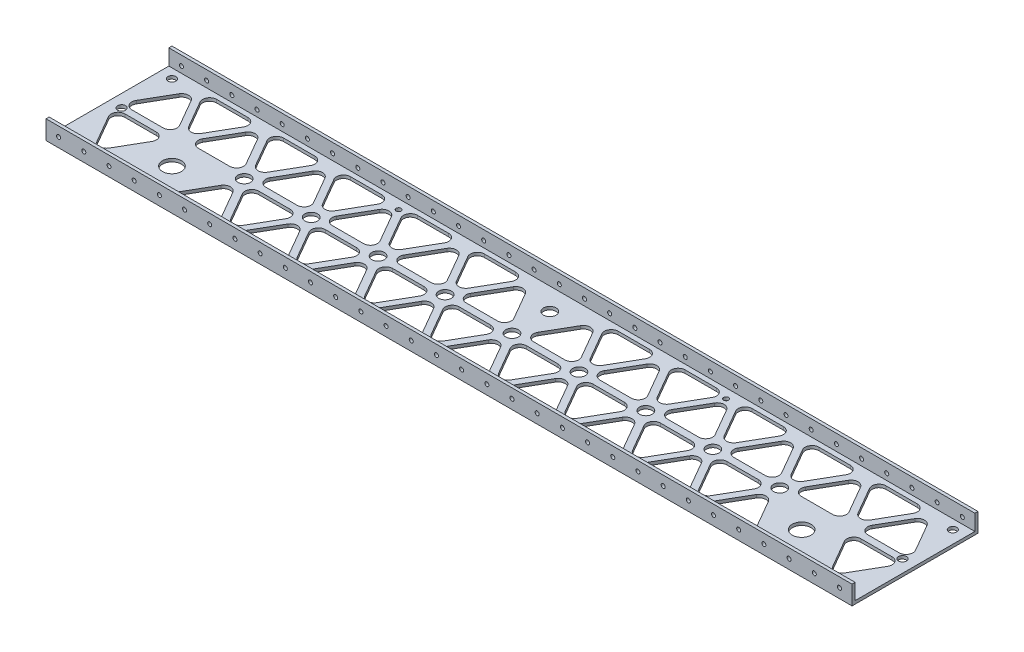
SolidWorks part; units mm, degrees
ref_plane "Front Plane" through (0, 0, 0) normal (0, 0, 1) x (1, 0, 0)
ref_plane "Top Plane" through (0, 0, 0) normal (0, 1, 0) x (1, 0, 0)
ref_plane "Right Plane" through (0, 0, 0) normal (1, 0, 0) x (0, 0, -1)
ref_plane "Plane1" through (0, -6.35, 0) normal (0, 1, 0) x (1, 0, 0)
sketch "Sketch1" plane through (0, -6.35, 0) normal (0, 1, 0) x (1, 0, 0)
  line L0 (-406.4, 63.5) -> (-406.4, -63.5)
  line L1 (-406.4, -63.5) -> (406.4, -63.5)
  line L2 (406.4, -63.5) -> (406.4, 63.5)
  line L3 (406.4, 63.5) -> (-406.4, 63.5)
extrude "Boss-Extrude1" add sketch "Sketch1" against normal blind 19.05
sketch "Sketch2" plane through (-406.4, 0, 0) normal (-1, 0, 0) x (0, 0, 1)
  line L0 (60.375, -6.35) -> (-60.375, -6.35)
  line L1 (-60.375, -6.35) -> (-60.375, -22.275)
  line L2 (-60.375, -22.275) -> (60.375, -22.275)
  line L3 (60.375, -22.275) -> (60.375, -6.35)
extrude "Cut-Extrude1" cut sketch "Sketch2" against normal through all
sketch "Sketch3" plane through (0, -22.275, 0) normal (0, 1, 0) x (-1, 0, 0)
  line L0 (-343.5622, -17.5) -> (-359.3671, -44.875)
  line L1 (-353.305, -55.375) -> (-321.695, -55.375)
  line L2 (-315.6329, -44.875) -> (-331.4378, -17.5)
  arc A0 (-359.3671, -44.875) -> (-353.305, -55.375) centre (-353.305, -48.375) ccw
  arc A1 (-321.695, -55.375) -> (-315.6329, -44.875) centre (-321.695, -48.375) ccw
  arc A2 (-331.4378, -17.5) -> (-343.5622, -17.5) centre (-337.5, -21) ccw
extrude "Cut-Extrude2" cut sketch "Sketch3" against normal through all
sketch "Sketch4" plane through (0, -22.275, 0) normal (0, 1, 0) x (-1, 0, 0)
  line L0 (-349.1414, 14) -> (-364.9463, 41.375)
  line L1 (-377.0707, 41.375) -> (-392.8756, 14)
  line L2 (-386.8135, 3.5) -> (-355.2035, 3.5)
  arc A0 (-364.9463, 41.375) -> (-377.0707, 41.375) centre (-371.0085, 37.875) ccw
  arc A1 (-392.8756, 14) -> (-386.8135, 3.5) centre (-386.8135, 10.5) ccw
  arc A2 (-355.2035, 3.5) -> (-349.1414, 14) centre (-355.2035, 10.5) ccw
extrude "Cut-Extrude3" cut sketch "Sketch4" against normal through all
sketch "Sketch5" plane through (0, -22.275, 0) normal (0, 1, 0) x (-1, 0, 0)
  line L0 (-364.9463, -41.375) -> (-349.1414, -14)
  line L1 (-355.2035, -3.5) -> (-386.8135, -3.5)
  line L2 (-392.8756, -14) -> (-377.0707, -41.375)
  arc A0 (-349.1414, -14) -> (-355.2035, -3.5) centre (-355.2035, -10.5) ccw
  arc A1 (-386.8135, -3.5) -> (-392.8756, -14) centre (-386.8135, -10.5) ccw
  arc A2 (-377.0707, -41.375) -> (-364.9463, -41.375) centre (-371.0085, -37.875) ccw
extrude "Cut-Extrude4" cut sketch "Sketch5" against normal through all
sketch "Sketch6" plane through (0, -22.275, 0) normal (0, 1, 0) x (-1, 0, 0)
  line L0 (364.9463, 41.375) -> (349.1414, 14)
  line L1 (355.2035, 3.5) -> (386.8135, 3.5)
  line L2 (392.8756, 14) -> (377.0707, 41.375)
  arc A0 (349.1414, 14) -> (355.2035, 3.5) centre (355.2035, 10.5) ccw
  arc A1 (386.8135, 3.5) -> (392.8756, 14) centre (386.8135, 10.5) ccw
  arc A2 (377.0707, 41.375) -> (364.9463, 41.375) centre (371.0085, 37.875) ccw
extrude "Cut-Extrude5" cut sketch "Sketch6" against normal through all
sketch "Sketch7" plane through (0, -22.275, 0) normal (0, 1, 0) x (-1, 0, 0)
  line L0 (349.1414, -14) -> (364.9463, -41.375)
  line L1 (377.0707, -41.375) -> (392.8756, -14)
  line L2 (386.8135, -3.5) -> (355.2035, -3.5)
  arc A0 (364.9463, -41.375) -> (377.0707, -41.375) centre (371.0085, -37.875) ccw
  arc A1 (392.8756, -14) -> (386.8135, -3.5) centre (386.8135, -10.5) ccw
  arc A2 (355.2035, -3.5) -> (349.1414, -14) centre (355.2035, -10.5) ccw
extrude "Cut-Extrude6" cut sketch "Sketch7" against normal through all
sketch "Sketch8" plane through (0, -22.275, 0) normal (0, 1, 0) x (-1, 0, 0)
  line L0 (331.4378, -17.5) -> (315.6329, -44.875)
  line L1 (321.695, -55.375) -> (353.305, -55.375)
  line L2 (359.3671, -44.875) -> (343.5622, -17.5)
  arc A0 (315.6329, -44.875) -> (321.695, -55.375) centre (321.695, -48.375) ccw
  arc A1 (353.305, -55.375) -> (359.3671, -44.875) centre (353.305, -48.375) ccw
  arc A2 (343.5622, -17.5) -> (331.4378, -17.5) centre (337.5, -21) ccw
extrude "Cut-Extrude7" cut sketch "Sketch8" against normal through all
sketch "Sketch9" plane through (0, -22.275, 0) normal (0, 1, 0) x (-1, 0, 0)
  line L0 (285.805, 55.375) -> (254.195, 55.375)
  line L1 (248.1329, 44.875) -> (263.9378, 17.5)
  line L2 (276.0622, 17.5) -> (291.8671, 44.875)
  arc A0 (254.195, 55.375) -> (248.1329, 44.875) centre (254.195, 48.375) ccw
  arc A1 (263.9378, 17.5) -> (276.0622, 17.5) centre (270, 21) ccw
  arc A2 (291.8671, 44.875) -> (285.805, 55.375) centre (285.805, 48.375) ccw
extrude "Cut-Extrude8" cut sketch "Sketch9" against normal through all
sketch "Sketch10" plane through (0, -22.275, 0) normal (0, 1, 0) x (-1, 0, 0)
  line L0 (190.8586, 14) -> (175.0537, 41.375)
  line L1 (162.9293, 41.375) -> (147.1244, 14)
  line L2 (153.1865, 3.5) -> (184.7965, 3.5)
  arc A0 (175.0537, 41.375) -> (162.9293, 41.375) centre (168.9915, 37.875) ccw
  arc A1 (147.1244, 14) -> (153.1865, 3.5) centre (153.1865, 10.5) ccw
  arc A2 (184.7965, 3.5) -> (190.8586, 14) centre (184.7965, 10.5) ccw
extrude "Cut-Extrude9" cut sketch "Sketch10" against normal through all
sketch "Sketch11" plane through (0, -22.275, 0) normal (0, 1, 0) x (-1, 0, 0)
  line L0 (-276.0622, -17.5) -> (-291.8671, -44.875)
  line L1 (-285.805, -55.375) -> (-254.195, -55.375)
  line L2 (-248.1329, -44.875) -> (-263.9378, -17.5)
  arc A0 (-291.8671, -44.875) -> (-285.805, -55.375) centre (-285.805, -48.375) ccw
  arc A1 (-254.195, -55.375) -> (-248.1329, -44.875) centre (-254.195, -48.375) ccw
  arc A2 (-263.9378, -17.5) -> (-276.0622, -17.5) centre (-270, -21) ccw
extrude "Cut-Extrude10" cut sketch "Sketch11" against normal through all
sketch "Sketch12" plane through (0, -22.275, 0) normal (0, 1, 0) x (-1, 0, 0)
  line L0 (61.4378, -17.5) -> (45.6329, -44.875)
  line L1 (51.695, -55.375) -> (83.305, -55.375)
  line L2 (89.3671, -44.875) -> (73.5622, -17.5)
  arc A0 (45.6329, -44.875) -> (51.695, -55.375) centre (51.695, -48.375) ccw
  arc A1 (83.305, -55.375) -> (89.3671, -44.875) centre (83.305, -48.375) ccw
  arc A2 (73.5622, -17.5) -> (61.4378, -17.5) centre (67.5, -21) ccw
extrude "Cut-Extrude11" cut sketch "Sketch12" against normal through all
sketch "Sketch13" plane through (0, -22.275, 0) normal (0, 1, 0) x (-1, 0, 0)
  line L0 (-214.1414, 14) -> (-229.9463, 41.375)
  line L1 (-242.0707, 41.375) -> (-257.8756, 14)
  line L2 (-251.8135, 3.5) -> (-220.2035, 3.5)
  arc A0 (-229.9463, 41.375) -> (-242.0707, 41.375) centre (-236.0085, 37.875) ccw
  arc A1 (-257.8756, 14) -> (-251.8135, 3.5) centre (-251.8135, 10.5) ccw
  arc A2 (-220.2035, 3.5) -> (-214.1414, 14) centre (-220.2035, 10.5) ccw
extrude "Cut-Extrude12" cut sketch "Sketch13" against normal through all
sketch "Sketch14" plane through (0, -22.275, 0) normal (0, 1, 0) x (-1, 0, 0)
  line L0 (83.305, 55.375) -> (51.695, 55.375)
  line L1 (45.6329, 44.875) -> (61.4378, 17.5)
  line L2 (73.5622, 17.5) -> (89.3671, 44.875)
  arc A0 (51.695, 55.375) -> (45.6329, 44.875) centre (51.695, 48.375) ccw
  arc A1 (61.4378, 17.5) -> (73.5622, 17.5) centre (67.5, 21) ccw
  arc A2 (89.3671, 44.875) -> (83.305, 55.375) centre (83.305, 48.375) ccw
extrude "Cut-Extrude13" cut sketch "Sketch14" against normal through all
sketch "Sketch15" plane through (0, -22.275, 0) normal (0, 1, 0) x (-1, 0, 0)
  line L0 (-325.8586, -14) -> (-310.0537, -41.375)
  line L1 (-297.9293, -41.375) -> (-282.1244, -14)
  line L2 (-288.1865, -3.5) -> (-319.7965, -3.5)
  arc A0 (-310.0537, -41.375) -> (-297.9293, -41.375) centre (-303.9915, -37.875) ccw
  arc A1 (-282.1244, -14) -> (-288.1865, -3.5) centre (-288.1865, -10.5) ccw
  arc A2 (-319.7965, -3.5) -> (-325.8586, -14) centre (-319.7965, -10.5) ccw
extrude "Cut-Extrude14" cut sketch "Sketch15" against normal through all
sketch "Sketch16" plane through (0, -22.275, 0) normal (0, 1, 0) x (-1, 0, 0)
  line L0 (263.9378, -17.5) -> (248.1329, -44.875)
  line L1 (254.195, -55.375) -> (285.805, -55.375)
  line L2 (291.8671, -44.875) -> (276.0622, -17.5)
  arc A0 (248.1329, -44.875) -> (254.195, -55.375) centre (254.195, -48.375) ccw
  arc A1 (285.805, -55.375) -> (291.8671, -44.875) centre (285.805, -48.375) ccw
  arc A2 (276.0622, -17.5) -> (263.9378, -17.5) centre (270, -21) ccw
extrude "Cut-Extrude15" cut sketch "Sketch16" against normal through all
sketch "Sketch17" plane through (0, -22.275, 0) normal (0, 1, 0) x (-1, 0, 0)
  line L0 (-254.195, 55.375) -> (-285.805, 55.375)
  line L1 (-291.8671, 44.875) -> (-276.0622, 17.5)
  line L2 (-263.9378, 17.5) -> (-248.1329, 44.875)
  arc A0 (-285.805, 55.375) -> (-291.8671, 44.875) centre (-285.805, 48.375) ccw
  arc A1 (-276.0622, 17.5) -> (-263.9378, 17.5) centre (-270, 21) ccw
  arc A2 (-248.1329, 44.875) -> (-254.195, 55.375) centre (-254.195, 48.375) ccw
extrude "Cut-Extrude16" cut sketch "Sketch17" against normal through all
sketch "Sketch18" plane through (0, -22.275, 0) normal (0, 1, 0) x (-1, 0, 0)
  line L0 (-51.695, 55.375) -> (-83.305, 55.375)
  line L1 (-89.3671, 44.875) -> (-73.5622, 17.5)
  line L2 (-61.4378, 17.5) -> (-45.6329, 44.875)
  arc A0 (-83.305, 55.375) -> (-89.3671, 44.875) centre (-83.305, 48.375) ccw
  arc A1 (-73.5622, 17.5) -> (-61.4378, 17.5) centre (-67.5, 21) ccw
  arc A2 (-45.6329, 44.875) -> (-51.695, 55.375) centre (-51.695, 48.375) ccw
extrude "Cut-Extrude17" cut sketch "Sketch18" against normal through all
sketch "Sketch19" plane through (0, -22.275, 0) normal (0, 1, 0) x (-1, 0, 0)
  line L0 (-190.8586, -14) -> (-175.0537, -41.375)
  line L1 (-162.9293, -41.375) -> (-147.1244, -14)
  line L2 (-153.1865, -3.5) -> (-184.7965, -3.5)
  arc A0 (-175.0537, -41.375) -> (-162.9293, -41.375) centre (-168.9915, -37.875) ccw
  arc A1 (-147.1244, -14) -> (-153.1865, -3.5) centre (-153.1865, -10.5) ccw
  arc A2 (-184.7965, -3.5) -> (-190.8586, -14) centre (-184.7965, -10.5) ccw
extrude "Cut-Extrude18" cut sketch "Sketch19" against normal through all
sketch "Sketch20" plane through (0, -22.275, 0) normal (0, 1, 0) x (-1, 0, 0)
  line L0 (175.0537, -41.375) -> (190.8586, -14)
  line L1 (184.7965, -3.5) -> (153.1865, -3.5)
  line L2 (147.1244, -14) -> (162.9293, -41.375)
  arc A0 (190.8586, -14) -> (184.7965, -3.5) centre (184.7965, -10.5) ccw
  arc A1 (153.1865, -3.5) -> (147.1244, -14) centre (153.1865, -10.5) ccw
  arc A2 (162.9293, -41.375) -> (175.0537, -41.375) centre (168.9915, -37.875) ccw
extrude "Cut-Extrude19" cut sketch "Sketch20" against normal through all
sketch "Sketch21" plane through (0, -22.275, 0) normal (0, 1, 0) x (-1, 0, 0)
  line L0 (218.305, 55.375) -> (186.695, 55.375)
  line L1 (180.6329, 44.875) -> (196.4378, 17.5)
  line L2 (208.5622, 17.5) -> (224.3671, 44.875)
  arc A0 (186.695, 55.375) -> (180.6329, 44.875) centre (186.695, 48.375) ccw
  arc A1 (196.4378, 17.5) -> (208.5622, 17.5) centre (202.5, 21) ccw
  arc A2 (224.3671, 44.875) -> (218.305, 55.375) centre (218.305, 48.375) ccw
extrude "Cut-Extrude20" cut sketch "Sketch21" against normal through all
sketch "Sketch22" plane through (0, -22.275, 0) normal (0, 1, 0) x (-1, 0, 0)
  line L0 (-55.8586, -14) -> (-40.0537, -41.375)
  line L1 (-27.9293, -41.375) -> (-12.1244, -14)
  line L2 (-18.1865, -3.5) -> (-49.7965, -3.5)
  arc A0 (-40.0537, -41.375) -> (-27.9293, -41.375) centre (-33.9915, -37.875) ccw
  arc A1 (-12.1244, -14) -> (-18.1865, -3.5) centre (-18.1865, -10.5) ccw
  arc A2 (-49.7965, -3.5) -> (-55.8586, -14) centre (-49.7965, -10.5) ccw
extrude "Cut-Extrude21" cut sketch "Sketch22" against normal through all
sketch "Sketch23" plane through (0, -22.275, 0) normal (0, 1, 0) x (-1, 0, 0)
  line L0 (-73.5622, -17.5) -> (-89.3671, -44.875)
  line L1 (-83.305, -55.375) -> (-51.695, -55.375)
  line L2 (-45.6329, -44.875) -> (-61.4378, -17.5)
  arc A0 (-89.3671, -44.875) -> (-83.305, -55.375) centre (-83.305, -48.375) ccw
  arc A1 (-51.695, -55.375) -> (-45.6329, -44.875) centre (-51.695, -48.375) ccw
  arc A2 (-61.4378, -17.5) -> (-73.5622, -17.5) centre (-67.5, -21) ccw
extrude "Cut-Extrude22" cut sketch "Sketch23" against normal through all
sketch "Sketch24" plane through (0, -22.275, 0) normal (0, 1, 0) x (-1, 0, 0)
  line L0 (310.0537, -41.375) -> (325.8586, -14)
  line L1 (319.7965, -3.5) -> (288.1865, -3.5)
  line L2 (282.1244, -14) -> (297.9293, -41.375)
  arc A0 (325.8586, -14) -> (319.7965, -3.5) centre (319.7965, -10.5) ccw
  arc A1 (288.1865, -3.5) -> (282.1244, -14) centre (288.1865, -10.5) ccw
  arc A2 (297.9293, -41.375) -> (310.0537, -41.375) centre (303.9915, -37.875) ccw
extrude "Cut-Extrude23" cut sketch "Sketch24" against normal through all
sketch "Sketch25" plane through (0, -22.275, 0) normal (0, 1, 0) x (-1, 0, 0)
  line L0 (-40.0537, 41.375) -> (-55.8586, 14)
  line L1 (-49.7965, 3.5) -> (-18.1865, 3.5)
  line L2 (-12.1244, 14) -> (-27.9293, 41.375)
  arc A0 (-55.8586, 14) -> (-49.7965, 3.5) centre (-49.7965, 10.5) ccw
  arc A1 (-18.1865, 3.5) -> (-12.1244, 14) centre (-18.1865, 10.5) ccw
  arc A2 (-27.9293, 41.375) -> (-40.0537, 41.375) centre (-33.9915, 37.875) ccw
extrude "Cut-Extrude24" cut sketch "Sketch25" against normal through all
sketch "Sketch26" plane through (0, -22.275, 0) normal (0, 1, 0) x (-1, 0, 0)
  line L0 (214.1414, -14) -> (229.9463, -41.375)
  line L1 (242.0707, -41.375) -> (257.8756, -14)
  line L2 (251.8135, -3.5) -> (220.2035, -3.5)
  arc A0 (229.9463, -41.375) -> (242.0707, -41.375) centre (236.0085, -37.875) ccw
  arc A1 (257.8756, -14) -> (251.8135, -3.5) centre (251.8135, -10.5) ccw
  arc A2 (220.2035, -3.5) -> (214.1414, -14) centre (220.2035, -10.5) ccw
extrude "Cut-Extrude25" cut sketch "Sketch26" against normal through all
sketch "Sketch27" plane through (0, -22.275, 0) normal (0, 1, 0) x (-1, 0, 0)
  line L0 (128.9378, -17.5) -> (113.1329, -44.875)
  line L1 (119.195, -55.375) -> (150.805, -55.375)
  line L2 (156.8671, -44.875) -> (141.0622, -17.5)
  arc A0 (113.1329, -44.875) -> (119.195, -55.375) centre (119.195, -48.375) ccw
  arc A1 (150.805, -55.375) -> (156.8671, -44.875) centre (150.805, -48.375) ccw
  arc A2 (141.0622, -17.5) -> (128.9378, -17.5) centre (135, -21) ccw
extrude "Cut-Extrude26" cut sketch "Sketch27" against normal through all
sketch "Sketch28" plane through (0, -22.275, 0) normal (0, 1, 0) x (-1, 0, 0)
  line L0 (229.9463, 41.375) -> (214.1414, 14)
  line L1 (220.2035, 3.5) -> (251.8135, 3.5)
  line L2 (257.8756, 14) -> (242.0707, 41.375)
  arc A0 (214.1414, 14) -> (220.2035, 3.5) centre (220.2035, 10.5) ccw
  arc A1 (251.8135, 3.5) -> (257.8756, 14) centre (251.8135, 10.5) ccw
  arc A2 (242.0707, 41.375) -> (229.9463, 41.375) centre (236.0085, 37.875) ccw
extrude "Cut-Extrude27" cut sketch "Sketch28" against normal through all
sketch "Sketch29" plane through (0, -22.275, 0) normal (0, 1, 0) x (-1, 0, 0)
  line L0 (-229.9463, -41.375) -> (-214.1414, -14)
  line L1 (-220.2035, -3.5) -> (-251.8135, -3.5)
  line L2 (-257.8756, -14) -> (-242.0707, -41.375)
  arc A0 (-214.1414, -14) -> (-220.2035, -3.5) centre (-220.2035, -10.5) ccw
  arc A1 (-251.8135, -3.5) -> (-257.8756, -14) centre (-251.8135, -10.5) ccw
  arc A2 (-242.0707, -41.375) -> (-229.9463, -41.375) centre (-236.0085, -37.875) ccw
extrude "Cut-Extrude28" cut sketch "Sketch29" against normal through all
sketch "Sketch30" plane through (0, -22.275, 0) normal (0, 1, 0) x (-1, 0, 0)
  line L0 (150.805, 55.375) -> (119.195, 55.375)
  line L1 (113.1329, 44.875) -> (128.9378, 17.5)
  line L2 (141.0622, 17.5) -> (156.8671, 44.875)
  arc A0 (119.195, 55.375) -> (113.1329, 44.875) centre (119.195, 48.375) ccw
  arc A1 (128.9378, 17.5) -> (141.0622, 17.5) centre (135, 21) ccw
  arc A2 (156.8671, 44.875) -> (150.805, 55.375) centre (150.805, 48.375) ccw
extrude "Cut-Extrude29" cut sketch "Sketch30" against normal through all
sketch "Sketch31" plane through (0, -22.275, 0) normal (0, 1, 0) x (-1, 0, 0)
  line L0 (15.805, 55.375) -> (-15.805, 55.375)
  line L1 (-21.8671, 44.875) -> (-6.0622, 17.5)
  line L2 (6.0622, 17.5) -> (21.8671, 44.875)
  arc A0 (-15.805, 55.375) -> (-21.8671, 44.875) centre (-15.805, 48.375) ccw
  arc A1 (-6.0622, 17.5) -> (6.0622, 17.5) centre (0, 21) ccw
  arc A2 (21.8671, 44.875) -> (15.805, 55.375) centre (15.805, 48.375) ccw
extrude "Cut-Extrude30" cut sketch "Sketch31" against normal through all
sketch "Sketch32" plane through (0, -22.275, 0) normal (0, 1, 0) x (-1, 0, 0)
  line L0 (94.9463, 41.375) -> (79.1414, 14)
  line L1 (85.2035, 3.5) -> (116.8135, 3.5)
  line L2 (122.8756, 14) -> (107.0707, 41.375)
  arc A0 (79.1414, 14) -> (85.2035, 3.5) centre (85.2035, 10.5) ccw
  arc A1 (116.8135, 3.5) -> (122.8756, 14) centre (116.8135, 10.5) ccw
  arc A2 (107.0707, 41.375) -> (94.9463, 41.375) centre (101.0085, 37.875) ccw
extrude "Cut-Extrude31" cut sketch "Sketch32" against normal through all
sketch "Sketch33" plane through (0, -22.275, 0) normal (0, 1, 0) x (-1, 0, 0)
  line L0 (55.8586, 14) -> (40.0537, 41.375)
  line L1 (27.9293, 41.375) -> (12.1244, 14)
  line L2 (18.1865, 3.5) -> (49.7965, 3.5)
  arc A0 (40.0537, 41.375) -> (27.9293, 41.375) centre (33.9915, 37.875) ccw
  arc A1 (12.1244, 14) -> (18.1865, 3.5) centre (18.1865, 10.5) ccw
  arc A2 (49.7965, 3.5) -> (55.8586, 14) centre (49.7965, 10.5) ccw
extrude "Cut-Extrude32" cut sketch "Sketch33" against normal through all
sketch "Sketch34" plane through (0, -22.275, 0) normal (0, 1, 0) x (-1, 0, 0)
  line L0 (79.1414, -14) -> (94.9463, -41.375)
  line L1 (107.0707, -41.375) -> (122.8756, -14)
  line L2 (116.8135, -3.5) -> (85.2035, -3.5)
  arc A0 (94.9463, -41.375) -> (107.0707, -41.375) centre (101.0085, -37.875) ccw
  arc A1 (122.8756, -14) -> (116.8135, -3.5) centre (116.8135, -10.5) ccw
  arc A2 (85.2035, -3.5) -> (79.1414, -14) centre (85.2035, -10.5) ccw
extrude "Cut-Extrude33" cut sketch "Sketch34" against normal through all
sketch "Sketch35" plane through (0, -22.275, 0) normal (0, 1, 0) x (-1, 0, 0)
  line L0 (40.0537, -41.375) -> (55.8586, -14)
  line L1 (49.7965, -3.5) -> (18.1865, -3.5)
  line L2 (12.1244, -14) -> (27.9293, -41.375)
  arc A0 (55.8586, -14) -> (49.7965, -3.5) centre (49.7965, -10.5) ccw
  arc A1 (18.1865, -3.5) -> (12.1244, -14) centre (18.1865, -10.5) ccw
  arc A2 (27.9293, -41.375) -> (40.0537, -41.375) centre (33.9915, -37.875) ccw
extrude "Cut-Extrude34" cut sketch "Sketch35" against normal through all
sketch "Sketch36" plane through (0, -22.275, 0) normal (0, 1, 0) x (-1, 0, 0)
  line L0 (-94.9463, -41.375) -> (-79.1414, -14)
  line L1 (-85.2035, -3.5) -> (-116.8135, -3.5)
  line L2 (-122.8756, -14) -> (-107.0707, -41.375)
  arc A0 (-79.1414, -14) -> (-85.2035, -3.5) centre (-85.2035, -10.5) ccw
  arc A1 (-116.8135, -3.5) -> (-122.8756, -14) centre (-116.8135, -10.5) ccw
  arc A2 (-107.0707, -41.375) -> (-94.9463, -41.375) centre (-101.0085, -37.875) ccw
extrude "Cut-Extrude35" cut sketch "Sketch36" against normal through all
sketch "Sketch37" plane through (0, -22.275, 0) normal (0, 1, 0) x (-1, 0, 0)
  line L0 (-119.195, 55.375) -> (-150.805, 55.375)
  line L1 (-156.8671, 44.875) -> (-141.0622, 17.5)
  line L2 (-128.9378, 17.5) -> (-113.1329, 44.875)
  arc A0 (-150.805, 55.375) -> (-156.8671, 44.875) centre (-150.805, 48.375) ccw
  arc A1 (-141.0622, 17.5) -> (-128.9378, 17.5) centre (-135, 21) ccw
  arc A2 (-113.1329, 44.875) -> (-119.195, 55.375) centre (-119.195, 48.375) ccw
extrude "Cut-Extrude36" cut sketch "Sketch37" against normal through all
sketch "Sketch38" plane through (0, -22.275, 0) normal (0, 1, 0) x (-1, 0, 0)
  line L0 (-175.0537, 41.375) -> (-190.8586, 14)
  line L1 (-184.7965, 3.5) -> (-153.1865, 3.5)
  line L2 (-147.1244, 14) -> (-162.9293, 41.375)
  arc A0 (-190.8586, 14) -> (-184.7965, 3.5) centre (-184.7965, 10.5) ccw
  arc A1 (-153.1865, 3.5) -> (-147.1244, 14) centre (-153.1865, 10.5) ccw
  arc A2 (-162.9293, 41.375) -> (-175.0537, 41.375) centre (-168.9915, 37.875) ccw
extrude "Cut-Extrude37" cut sketch "Sketch38" against normal through all
sketch "Sketch39" plane through (0, -22.275, 0) normal (0, 1, 0) x (-1, 0, 0)
  line L0 (-208.5622, -17.5) -> (-224.3671, -44.875)
  line L1 (-218.305, -55.375) -> (-186.695, -55.375)
  line L2 (-180.6329, -44.875) -> (-196.4378, -17.5)
  arc A0 (-224.3671, -44.875) -> (-218.305, -55.375) centre (-218.305, -48.375) ccw
  arc A1 (-186.695, -55.375) -> (-180.6329, -44.875) centre (-186.695, -48.375) ccw
  arc A2 (-196.4378, -17.5) -> (-208.5622, -17.5) centre (-202.5, -21) ccw
extrude "Cut-Extrude38" cut sketch "Sketch39" against normal through all
sketch "Sketch40" plane through (0, -22.275, 0) normal (0, 1, 0) x (-1, 0, 0)
  line L0 (-79.1414, 14) -> (-94.9463, 41.375)
  line L1 (-107.0707, 41.375) -> (-122.8756, 14)
  line L2 (-116.8135, 3.5) -> (-85.2035, 3.5)
  arc A0 (-94.9463, 41.375) -> (-107.0707, 41.375) centre (-101.0085, 37.875) ccw
  arc A1 (-122.8756, 14) -> (-116.8135, 3.5) centre (-116.8135, 10.5) ccw
  arc A2 (-85.2035, 3.5) -> (-79.1414, 14) centre (-85.2035, 10.5) ccw
extrude "Cut-Extrude39" cut sketch "Sketch40" against normal through all
sketch "Sketch41" plane through (0, -22.275, 0) normal (0, 1, 0) x (-1, 0, 0)
  line L0 (-186.695, 55.375) -> (-218.305, 55.375)
  line L1 (-224.3671, 44.875) -> (-208.5622, 17.5)
  line L2 (-196.4378, 17.5) -> (-180.6329, 44.875)
  arc A0 (-218.305, 55.375) -> (-224.3671, 44.875) centre (-218.305, 48.375) ccw
  arc A1 (-208.5622, 17.5) -> (-196.4378, 17.5) centre (-202.5, 21) ccw
  arc A2 (-180.6329, 44.875) -> (-186.695, 55.375) centre (-186.695, 48.375) ccw
extrude "Cut-Extrude40" cut sketch "Sketch41" against normal through all
sketch "Sketch42" plane through (0, -22.275, 0) normal (0, 1, 0) x (-1, 0, 0)
  line L0 (196.4378, -17.5) -> (180.6329, -44.875)
  line L1 (186.695, -55.375) -> (218.305, -55.375)
  line L2 (224.3671, -44.875) -> (208.5622, -17.5)
  arc A0 (180.6329, -44.875) -> (186.695, -55.375) centre (186.695, -48.375) ccw
  arc A1 (218.305, -55.375) -> (224.3671, -44.875) centre (218.305, -48.375) ccw
  arc A2 (208.5622, -17.5) -> (196.4378, -17.5) centre (202.5, -21) ccw
extrude "Cut-Extrude41" cut sketch "Sketch42" against normal through all
sketch "Sketch43" plane through (0, -25.4, 0) normal (0, -1, 0) x (1, 0, 0)
  line L0 (128.9378, -17.5) -> (113.1329, -44.875)
  line L1 (119.195, -55.375) -> (150.805, -55.375)
  line L2 (156.8671, -44.875) -> (141.0622, -17.5)
  arc A0 (113.1329, -44.875) -> (119.195, -55.375) centre (119.195, -48.375) ccw
  arc A1 (150.805, -55.375) -> (156.8671, -44.875) centre (150.805, -48.375) ccw
  arc A2 (141.0622, -17.5) -> (128.9378, -17.5) centre (135, -21) ccw
extrude "Cut-Extrude42" cut sketch "Sketch43" against normal through all
hole_wizard "3/4 (0.75) Diameter Hole1" positions "Sketch45" profile "Sketch44" hole size "3/4" standard "ANSI Inch"
sketch "Sketch45" plane through (0, -22.275, 0) normal (0, 1, 0) x (1, 0, 0)
  point P0 (317.5, -25.4)
  point P1 (-317.5, -25.4)
sketch "Sketch44" plane through (317.5, -22.275, 25.4) normal (1, 0, 0) x (0, 0, 1)
  line L0 (0, 0) -> (0, 3.125)
  line L1 (0, 3.125) -> (9.525, 3.125)
  line L2 (9.525, 3.125) -> (9.525, 0)
  line L5 (9.525, 0) -> (0, 0)
  line L11 (0, -6.35) -> (0, 107.95) construction
  dimension "Thru Hole Dia." = 19.05
  dimension "Thru Hole Depth" = 3.125
hole_wizard "#10 Clearance Hole1" positions "Sketch47" profile "Sketch46" hole size "#10" standard "ANSI Inch"
sketch "Sketch47" plane through (0, -22.275, 0) normal (0, 1, 0) x (1, 0, 0)
  point P0 (165.1, 50.8)
  point P1 (165.1, -50.8)
  point P2 (-165.1, 50.8)
  point P3 (-165.1, -50.8)
sketch "Sketch46" plane through (165.1, -22.275, -50.8) normal (1, 0, 0) x (0, 0, 1)
  line L0 (0, 0) -> (0, 3.125)
  line L1 (0, 3.125) -> (2.5, 3.125)
  line L2 (2.5, 3.125) -> (2.5, 0)
  line L5 (2.5, 0) -> (0, 0)
  line L11 (0, -6.35) -> (0, 107.95) construction
  dimension "Thru Hole Dia." = 5
  dimension "Thru Hole Depth" = 3.125
hole_wizard "Hole1" positions "Sketch49" profile "Sketch48" legacy
sketch "Sketch49" plane through (0, -22.275, 0) normal (0, 1, 0) x (1, 0, 0)
  point P0 (393.7, 50.8)
  point P1 (393.7, 0)
  point P2 (-393.7, 50.8)
  point P3 (-393.7, 0)
sketch "Sketch48" plane through (393.7, -22.275, -50.8) normal (1, 0, 0) x (0, 0, 1)
  line L0 (0, 0) -> (0, 3.125)
  line L1 (0, 3.125) -> (4, 3.125)
  line L2 (4, 3.125) -> (4, 0)
  line L3 (4, 0) -> (0, 0)
  line L4 (0, 110) -> (0, -10) construction
  dimension "Diameter" = 8
  dimension "Depth" = 3.125
hole_wizard "#6 Clearance Hole1" positions "Sketch51" profile "Sketch50" hole size "#6" standard "ANSI Inch"
sketch "Sketch51" plane through (0, 0, 60.375) normal (0, 0, -1) x (-1, 0, 0)
  point P0 (-393.7, -15.875)
  point P1 (-368.3, -15.875)
  point P2 (-342.9, -15.875)
  point P3 (-317.5, -15.875)
  point P4 (-292.1, -15.875)
  point P5 (-266.7, -15.875)
  point P6 (-241.3, -15.875)
  point P7 (-215.9, -15.875)
  point P8 (-190.5, -15.875)
  point P9 (-165.1, -15.875)
  point P10 (-139.7, -15.875)
  point P11 (-114.3, -15.875)
  point P12 (-88.9, -15.875)
  point P13 (-63.5, -15.875)
  point P14 (-38.1, -15.875)
  point P15 (-12.7, -15.875)
  point P16 (12.7, -15.875)
  point P17 (38.1, -15.875)
  point P18 (63.5, -15.875)
  point P19 (88.9, -15.875)
  point P20 (114.3, -15.875)
  point P21 (139.7, -15.875)
  point P22 (165.1, -15.875)
  point P23 (190.5, -15.875)
  point P24 (215.9, -15.875)
  point P25 (241.3, -15.875)
  point P26 (266.7, -15.875)
  point P27 (292.1, -15.875)
  point P28 (317.5, -15.875)
  point P29 (342.9, -15.875)
  point P30 (368.3, -15.875)
  point P31 (393.7, -15.875)
sketch "Sketch50" plane through (393.7, -15.875, 60.375) normal (1, 0, 0) x (0, 1, 0)
  line L0 (0, 0) -> (0, 3.125)
  line L1 (0, 3.125) -> (2.032, 3.125)
  line L2 (2.032, 3.125) -> (2.032, 0)
  line L5 (2.032, 0) -> (0, 0)
  line L11 (0, -6.35) -> (0, 107.95) construction
  dimension "Thru Hole Dia." = 4.064
  dimension "Thru Hole Depth" = 3.125
hole_wizard "#6 Clearance Hole2" positions "Sketch53" profile "Sketch52" hole size "#6" standard "ANSI Inch"
sketch "Sketch53" plane through (0, 0, -63.5) normal (0, 0, -1) x (-1, 0, 0)
  point P0 (-393.7, -15.875)
  point P1 (-368.3, -15.875)
  point P2 (-342.9, -15.875)
  point P3 (-317.5, -15.875)
  point P4 (-292.1, -15.875)
  point P5 (-266.7, -15.875)
  point P6 (-241.3, -15.875)
  point P7 (-215.9, -15.875)
  point P8 (-190.5, -15.875)
  point P9 (-165.1, -15.875)
  point P10 (-139.7, -15.875)
  point P11 (-114.3, -15.875)
  point P12 (-88.9, -15.875)
  point P13 (-63.5, -15.875)
  point P14 (-38.1, -15.875)
  point P15 (-12.7, -15.875)
  point P16 (12.7, -15.875)
  point P17 (38.1, -15.875)
  point P18 (63.5, -15.875)
  point P19 (88.9, -15.875)
  point P20 (114.3, -15.875)
  point P21 (139.7, -15.875)
  point P22 (165.1, -15.875)
  point P23 (190.5, -15.875)
  point P24 (215.9, -15.875)
  point P25 (241.3, -15.875)
  point P26 (266.7, -15.875)
  point P27 (292.1, -15.875)
  point P28 (317.5, -15.875)
  point P29 (342.9, -15.875)
  point P30 (368.3, -15.875)
  point P31 (393.7, -15.875)
sketch "Sketch52" plane through (393.7, -15.875, -63.5) normal (1, 0, 0) x (0, 1, 0)
  line L0 (0, 0) -> (0, 127)
  line L1 (0, 127) -> (2.032, 127)
  line L2 (2.032, 127) -> (2.032, 0)
  line L5 (2.032, 0) -> (0, 0)
  line L11 (0, -6.35) -> (0, 107.95) construction
  dimension "Thru Hole Dia." = 4.064
  dimension "Thru Hole Depth" = 127
hole_wizard "1/2 (0.5) Diameter Hole1" positions "Sketch55" profile "Sketch54" hole size "1/2" standard "ANSI Inch"
sketch "Sketch55" plane through (0, -22.275, 0) normal (0, 1, 0) x (1, 0, 0)
  point P0 (270, 0)
  point P1 (202.5, 0)
  point P2 (135, 0)
  point P3 (67.5, 0)
  point P4 (-67.5, 0)
  point P5 (-135, 0)
  point P6 (-202.5, 0)
  point P7 (-270, 0)
  point P8 (0, 0)
  point P9 (0, 38.1)
sketch "Sketch54" plane through (270, -22.275, 0) normal (1, 0, 0) x (0, 0, 1)
  line L0 (0, 0) -> (0, 3.125)
  line L1 (0, 3.125) -> (6.35, 3.125)
  line L2 (6.35, 3.125) -> (6.35, 0)
  line L5 (6.35, 0) -> (0, 0)
  line L11 (0, -6.35) -> (0, 107.95) construction
  dimension "Thru Hole Dia." = 12.7
  dimension "Thru Hole Depth" = 3.125
